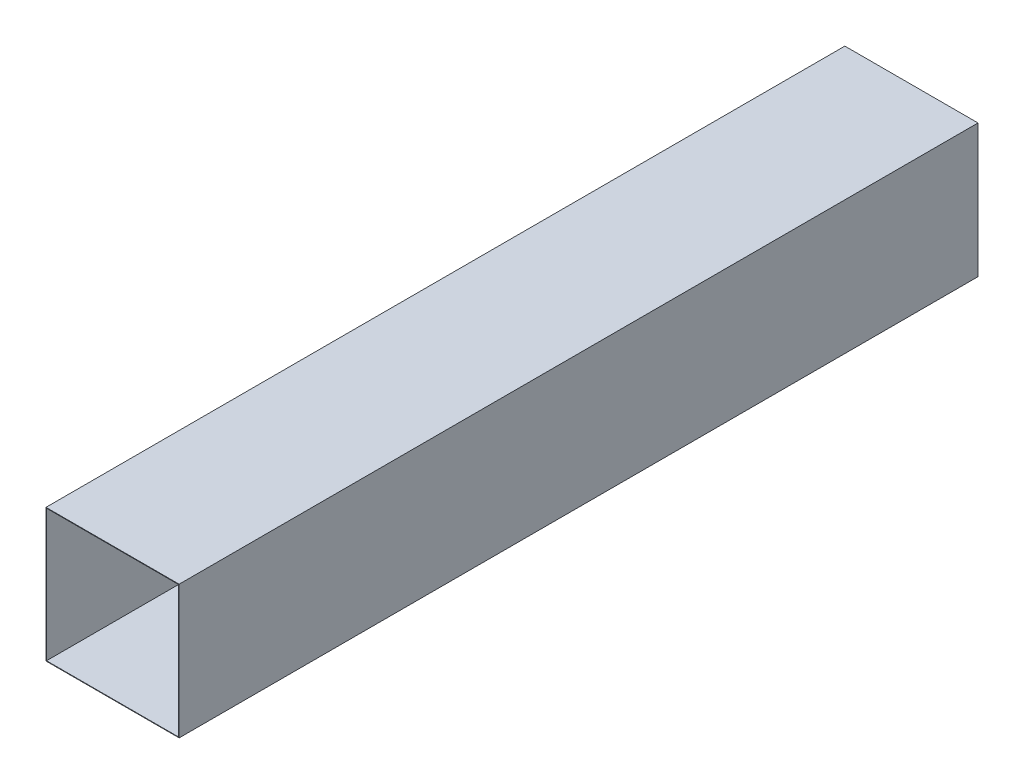
SolidWorks part; units mm, degrees
material "Plain Carbon Steel"
ref_plane "Front Plane" through (0, 0, 0) normal (0, 0, 1) x (1, 0, 0)
ref_plane "Top Plane" through (0, 0, 0) normal (0, 1, 0) x (1, 0, 0)
ref_plane "Right Plane" through (0, 0, 0) normal (1, 0, 0) x (0, 0, -1)
sketch "DuctSketch" plane through (0, 0, 0) normal (0, 0, 1) x (1, 0, 0)
  line L1 (-250, 250) -> (250, 250)
  line L2 (-250, 250) -> (-250, -250)
  line L3 (-250, -250) -> (250, -250)
  line L4 (250, 250) -> (250, -250)
  line L5 (-250, 250) -> (250, -250) construction
  line L6 (-250, -250) -> (250, 250) construction
  point P0 (0, 0)
  dimension "Height" = 500
  dimension "Width" = 500
extrude "Extrusion" add sketch "DuctSketch" along normal blind 3000 thin thin type one direction reverse wall 2
sketch "FilterSketch" plane through (0, 0, 0) normal (0, 0, -1) x (-1, 0, 0)
  line L1 (-250, -250) -> (250, -250)
  line L2 (-250, -250) -> (-250, 250)
  line L3 (-250, 250) -> (250, 250)
  line L4 (250, -250) -> (250, 250)
  dimension "NominalHeight" = 500
  dimension "NominalWidth" = 500
sketch "Sketch1" [suppressed] plane through (0, 0, 0) normal (0, 0, 1) x (1, 0, 0)
  point P0 (0, 0)
ref_axis "Axis1" [suppressed] through (0, 0, 0) along (0, 0, -1)
other "CPoint1" parameters "Diameter"=0, "StubLength"=1000
ref_axis "Axis2" through (0, 0, -10) along (0, 0, 1)
